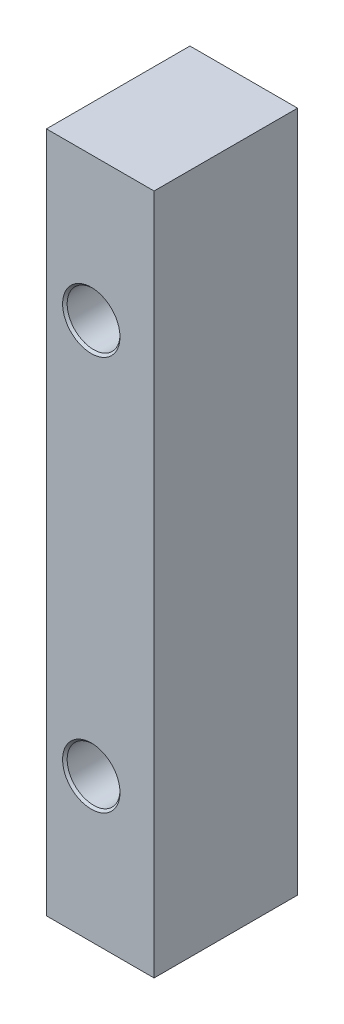
SolidWorks part; units mm, degrees
material "2024-T4"
ref_plane "Front" through (0, 0, 0) normal (0, 0, 1) x (1, 0, 0)
ref_plane "Top" through (0, 0, 0) normal (0, 1, 0) x (1, 0, 0)
ref_plane "Right" through (0, 0, 0) normal (1, 0, 0) x (0, 0, -1)
sketch "Эскиз1" plane through (0, 0, 0) normal (0, 0, 1) x (1, 0, 0)
  line L1 (-3, -19) -> (3, -19)
  line L2 (-3, -19) -> (-3, 19)
  line L3 (-3, 19) -> (3, 19)
  line L4 (3, -19) -> (3, 19)
  line L5 (-3, -19) -> (3, 19) construction
  line L6 (-3, 19) -> (3, -19) construction
  point P0 (0, 0)
  dimension "D1" = 6
  dimension "D2" = 38
extrude "Бобышка-Вытянуть1" add sketch "Эскиз1" along normal blind 8
hole_wizard "Цековка для  винта с внутренним шестигранником #41" positions "Эскиз3" profile "Эскиз2" counterbore size "#4" standard "Ansi (в дюймах)" end condition through all
sketch "Эскиз3" plane through (0, 0, 0) normal (0, 0, -1) x (-1, 0, 0)
  line L0 (-3, -19) -> (-3, 19) construction
  line L1 (-3, 19) -> (3, 19) construction
  point P0 (0.5, 11)
  point P1 (0.5, -11)
  dimension "D1" = 22
  dimension "D2" = 3.5
  dimension "D3" = 8
sketch "Эскиз2" plane through (-0.5, 11, 0) normal (1, 0, 0) x (0, 1, 0)
  line L0 (0, 0) -> (0, 8)
  line L1 (1.4732, 7.873) -> (1.6002, 8)
  line L2 (1.4732, 7.873) -> (1.4732, 2.9718)
  line L3 (1.4732, 2.9718) -> (1.6002, 2.8448)
  line L4 (1.6002, 2.8448) -> (2.7788, 2.8448)
  line L5 (2.7788, 2.8448) -> (2.7788, 0.127)
  line L6 (2.7788, 0.127) -> (2.9058, 0)
  line L7 (2.9058, 0) -> (0, 0)
  line L8 (-2.7788, 0.127) -> (-2.9058, 0) construction
  line L9 (-1.4732, 2.9718) -> (-1.6002, 2.8448) construction
  line L11 (0, -6.35) -> (0, 107.95) construction
  line L12 (1.6002, 8) -> (0, 8)
  line L13 (-1.4732, 7.873) -> (-1.6002, 8) construction
  dimension "Диаметр сквозного отверстия" = 2.9464
  dimension "Глубина сквозного отверстия" = 8
  dimension "Диаметр цековки" = 5.5575
  dimension "Глубина цековки" = 2.8448
  dimension "Диаметр передней зенковки" = 5.8115
  dimension "Угол передней зенковки" = 90
  dimension "Диаметр средней зенковки" = 3.2004
  dimension "Угол средней зенковки" = 90
  dimension "Диаметр задней зенковки" = 3.2004
  dimension "Угол задней зенковки" = 90
chamfer "Фаска1" distance 0.5 angle 64 4 edges at (-3, -9.7869, 1.4859) (-3, -12.2131, 1.4859) (-3, 9.7869, 1.4859) (-3, 12.2131, 1.4859) first distance on face at (-0.3606, -11, 1.4859) first distance on face at (-0.3606, 11, 1.4859)
